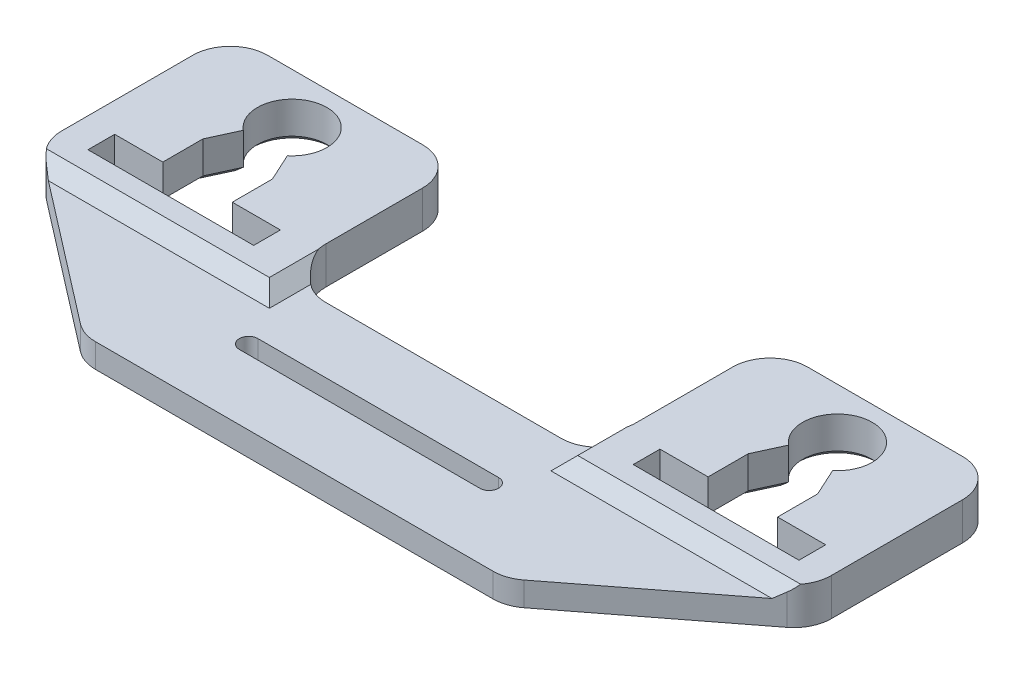
SolidWorks part; units mm, degrees
ref_plane "Front Plane" through (0, 0, 0) normal (0, 0, 1) x (1, 0, 0)
ref_plane "Top Plane" through (0, 0, 0) normal (0, 1, 0) x (1, 0, 0)
ref_plane "Right Plane" through (0, 0, 0) normal (1, 0, 0) x (0, 0, -1)
sketch "Sketch1" plane through (0, 0, 0) normal (0, 1, 0) x (1, 0, 0)
  line L0 (-55.125, 3.0679) -> (-57.5, -2.1087)
  line L1 (72, -17.5) -> (-72, -17.5)
  line L2 (72, -17.5) -> (72, 17.5)
  line L3 (72, 17.5) -> (-72, 17.5)
  line L4 (-72, -17.5) -> (-72, 17.5)
  line L5 (72, -17.5) -> (-72, 17.5) construction
  line L6 (72, 17.5) -> (-72, -17.5) construction
  line L7 (-57.5, -2.1087) -> (-57.5, -9.6087)
  line L8 (-57.5, -9.6087) -> (-66.5, -9.6087)
  line L9 (-66.5, -9.6087) -> (-66.5, -14.6087)
  line L10 (-66.5, -14.6087) -> (-35.5, -14.6087)
  line L11 (-51, 8.0913) -> (-51, -14.6087) construction
  line L12 (-35.5, -9.6087) -> (-35.5, -14.6087)
  line L13 (-44.5, -9.6087) -> (-35.5, -9.6087)
  line L14 (-44.5, -2.1087) -> (-44.5, -9.6087)
  line L15 (-46.875, 3.0679) -> (-44.5, -2.1087)
  line L16 (-66.5, -14.1087) -> (-35.5, -14.1087) construction
  line L17 (-61.3629, 14.0913) -> (-37.8704, 14.0913) construction
  line L18 (0, 32.8581) -> (0, -25.5534) construction
  line L19 (61.3629, 14.0913) -> (37.8704, 14.0913) construction
  line L20 (66.5, -14.1087) -> (35.5, -14.1087) construction
  line L21 (51, 8.0913) -> (51, -14.6087) construction
  line L22 (46.875, 3.0679) -> (44.5, -2.1087)
  line L23 (44.5, -2.1087) -> (44.5, -9.6087)
  line L24 (44.5, -9.6087) -> (35.5, -9.6087)
  line L25 (35.5, -9.6087) -> (35.5, -14.6087)
  line L26 (66.5, -14.6087) -> (35.5, -14.6087)
  line L27 (66.5, -9.6087) -> (66.5, -14.6087)
  line L28 (57.5, -9.6087) -> (66.5, -9.6087)
  line L29 (57.5, -2.1087) -> (57.5, -9.6087)
  line L30 (55.125, 3.0679) -> (57.5, -2.1087)
  arc A0 (-46.875, 3.0679) -> (-55.125, 3.0679) centre (-51, 8.0913) ccw
  circle A1 centre (-51, 8.0913) radius 6 construction
  circle A2 centre (51, 8.0913) radius 6 construction
  arc A3 (46.875, 3.0679) -> (55.125, 3.0679) centre (51, 8.0913) cw
  point P0 (0, 0)
  dimension "D6" = 13
  dimension "D8" = 12
  dimension "D1" = 35
  dimension "D2" = 51
  dimension "D3" = 13
  dimension "D4" = 5
  dimension "D5" = 31
  dimension "D7" = 0.5
  dimension "D9" = 28.2
  dimension "D10" = 7.5
  dimension "D11" = 144
  dimension "D12" = 8.25
extrude "Boss-Extrude1" add sketch "Sketch1" along normal blind 7
sketch "Sketch6" plane through (0, 7, 0) normal (0, 1, 0) x (1, 0, 0)
  line L2 (0, -64.1267) -> (0, 27.2818) construction
  line L6 (72, -17.5) -> (39.5771, -42.5)
  line L7 (39.5771, -42.5) -> (-39.5771, -42.5)
  line L8 (72, -17.5) -> (-72, -17.5)
  line L9 (-72, -17.5) -> (72, -17.5) construction
  line L10 (-72, -17.5) -> (-39.5771, -42.5)
  point P10 (0, -64.1267)
  point P11 (39.5771, -50.2954)
  point P15 (0, -17.5)
  point P16 (0, -42.5)
  dimension "D1" = 25
extrude "Boss-Extrude2" add sketch "Sketch6" against normal up to surface (7 mm away) up to face at (-51, 0, 5.421)
sketch "Sketch8" plane through (0, 7, 0) normal (0, 1, 0) x (1, 0, 0)
  line L0 (72, 17.5) -> (-72, 17.5) construction
  line L1 (-29, 17.5) -> (29, 17.5)
  line L2 (-29, 17.5) -> (-29, -14.6087)
  line L3 (-29, -14.6087) -> (29, -14.6087)
  line L4 (29, 17.5) -> (29, -14.6087)
  line L5 (35.5, -14.6087) -> (66.5, -14.6087) construction
  point P8 (0, 17.5)
  dimension "D1" = 58
extrude "Cut-Extrude5" cut sketch "Sketch8" against normal through all
fillet "Fillet1" radius 7 10 edges at (-72, 3.5, -17.5) (72, 3.5, -17.5) (29, 3.5, -17.5) (29, 3.5, 14.6087) (-29, 3.5, 14.6087) (-29, 3.5, -17.5) (72, 3.5, 17.5) (39.5771, 3.5, 42.5) (-72, 3.5, 17.5) (-39.5771, 3.5, 42.5)
sketch "Sketch4" plane through (0, 7, 0) normal (0, 1, 0) x (1, 0, 0)
  line L0 (-22.5, -28.5543) -> (22.5, -28.5543) construction
  line L1 (-22.5, -26.8043) -> (22.5, -26.8043)
  line L2 (-22.5, -30.3043) -> (22.5, -30.3043)
  line L3 (0, -14.6087) -> (0, -42.5) construction
  line L4 (-37.1917, -42.5) -> (37.1917, -42.5) construction
  line L5 (-22, -14.6087) -> (22, -14.6087) construction
  arc A0 (-22.5, -26.8043) -> (-22.5, -30.3043) centre (-22.5, -28.5543) ccw
  arc A1 (22.5, -30.3043) -> (22.5, -26.8043) centre (22.5, -28.5543) ccw
  point P2 (0, -28.5543)
  point P8 (0, -26.5798)
  point P9 (0, 0)
  point P10 (0, -14.6087)
  point P18 (0, -28.5543)
  dimension "D1" = 3.5
  dimension "D2" = 45
extrude "Cut-Extrude3" cut sketch "Sketch4" against normal through all
sketch "Sketch5" plane through (0, 7, 0) normal (0, 1, 0) x (1, 0, 0)
  line L0 (-28.8377, 35.8255) -> (-28.8377, -18.3331)
  line L5 (-28.8377, -18.3331) -> (-81.1605, -18.3331)
  line L6 (-81.1605, -18.3331) -> (-81.1605, -59.1815)
  line L7 (-81.1605, -59.1815) -> (81.1605, -59.1815)
  line L8 (-28.8377, 35.8255) -> (28.8377, 35.8255)
  line L9 (0, 44.546) -> (0, -69.9673) construction
  line L10 (81.1605, -18.3331) -> (81.1605, -59.1815)
  line L11 (28.8377, -18.3331) -> (81.1605, -18.3331)
  line L12 (28.8377, 35.8255) -> (28.8377, -18.3331)
  point P11 (0, 35.8255)
  point P12 (0, -59.1815)
extrude "Cut-Extrude4" cut sketch "Sketch5" against normal blind 2.5
chamfer "Chamfer2" distance 2.5 angle 45 4 edges at (28.8377, 4.5, 13.7201) (49.6904, 4.5, 18.3331) (-28.8377, 4.5, 13.7201) (-49.6904, 4.5, 18.3331)
chamfer "Chamfer3" distance 1 angle 45 20 edges at (-66.5, 0, 12.1087) (-62, 0, 9.6087) (-57.5, 0, 5.8587) (-56.3125, 0, -0.4796) (-51, 0, -14.5913) (-45.6875, 0, -0.4796) (-44.5, 0, 5.8587) (-40, 0, 9.6087) (-35.5, 0, 12.1087) (-51, 0, 14.6087) (66.5, 0, 12.1087) (62, 0, 9.6087) (57.5, 0, 5.8587) (56.3125, 0, -0.4796) (51, 0, -14.5913) (45.6875, 0, -0.4796) (44.5, 0, 5.8587) (40, 0, 9.6087) (35.5, 0, 12.1087) (51, 0, 14.6087)
